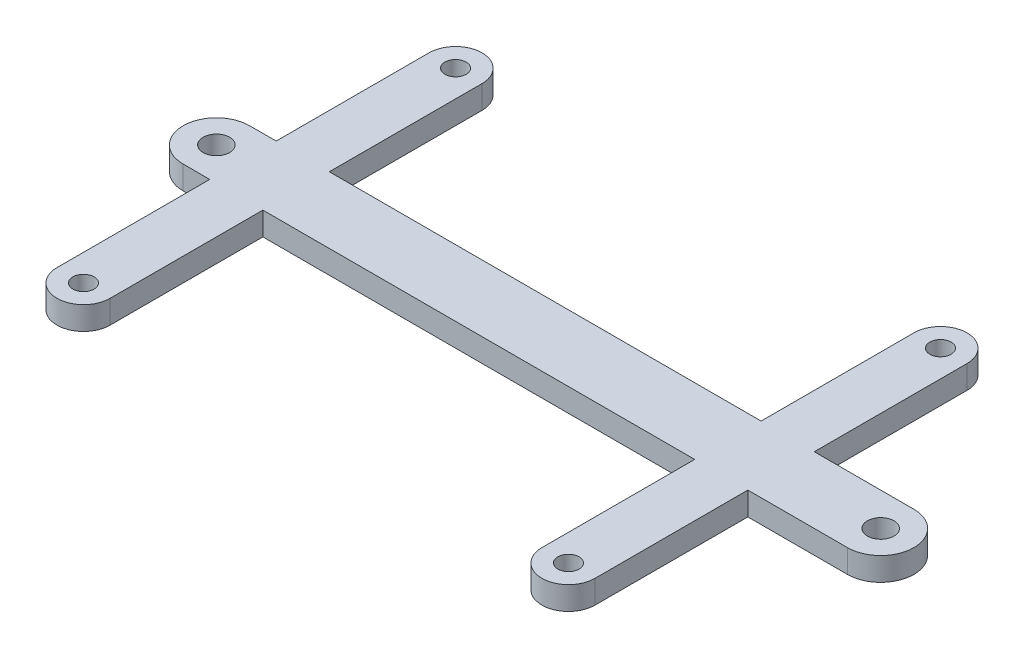
SolidWorks part; units mm, degrees
ref_plane "Front Plane" through (0, 0, 0) normal (0, 0, 1) x (1, 0, 0)
ref_plane "Top Plane" through (0, 0, 0) normal (0, 1, 0) x (1, 0, 0)
ref_plane "Right Plane" through (0, 0, 0) normal (1, 0, 0) x (0, 0, -1)
sketch "Sketch1" plane through (0, 0, 0) normal (0, 1, 0) x (1, 0, 0)
  line L0 (35, 28) -> (35, 5)
  line L4 (27, 28) -> (27, 5)
  line L5 (50, 5) -> (35, 5)
  line L16 (-50, 5) -> (-46, 5)
  line L17 (-38, 28) -> (-38, 5)
  line L18 (-46, 28) -> (-46, 5)
  line L19 (-38, 5) -> (27, 5)
  line L20 (0, 0) -> (15.6134, 0)
  line L21 (-38, -5) -> (27, -5)
  line L22 (-46, -28) -> (-46, -5)
  line L23 (-38, -28) -> (-38, -5)
  line L24 (50, -5) -> (35, -5)
  line L25 (27, -28) -> (27, -5)
  line L26 (35, -28) -> (35, -5)
  line L27 (-46, -5) -> (-50, -5)
  circle A0 centre (50, 0) radius 2
  arc A1 (50, -5) -> (50, 5) centre (50, 0) ccw
  arc A6 (-50, -5) -> (-50, 5) centre (-50, 0) cw
  circle A7 centre (-50, 0) radius 2
  circle A12 centre (31, 28) radius 1.6
  arc A13 (35, 28) -> (27, 28) centre (31, 28) ccw
  arc A14 (-38, 28) -> (-46, 28) centre (-42, 28) ccw
  circle A15 centre (-42, 28) radius 1.6
  circle A16 centre (-42, -28) radius 1.6
  arc A17 (-38, -28) -> (-46, -28) centre (-42, -28) cw
  arc A18 (35, -28) -> (27, -28) centre (31, -28) cw
  circle A19 centre (31, -28) radius 1.6
extrude "Boss-Extrude1" add sketch "Sketch1" along normal blind 3.5 contours A18 L26 L24 A1 L5 L0 A13 L4 L19 L17 A14 L18 L16 A6 L27 L22 A17 L23 L21 L25 A16 A15 A12 A0 A7 A19 region at (-2.3813, 0, 0)
